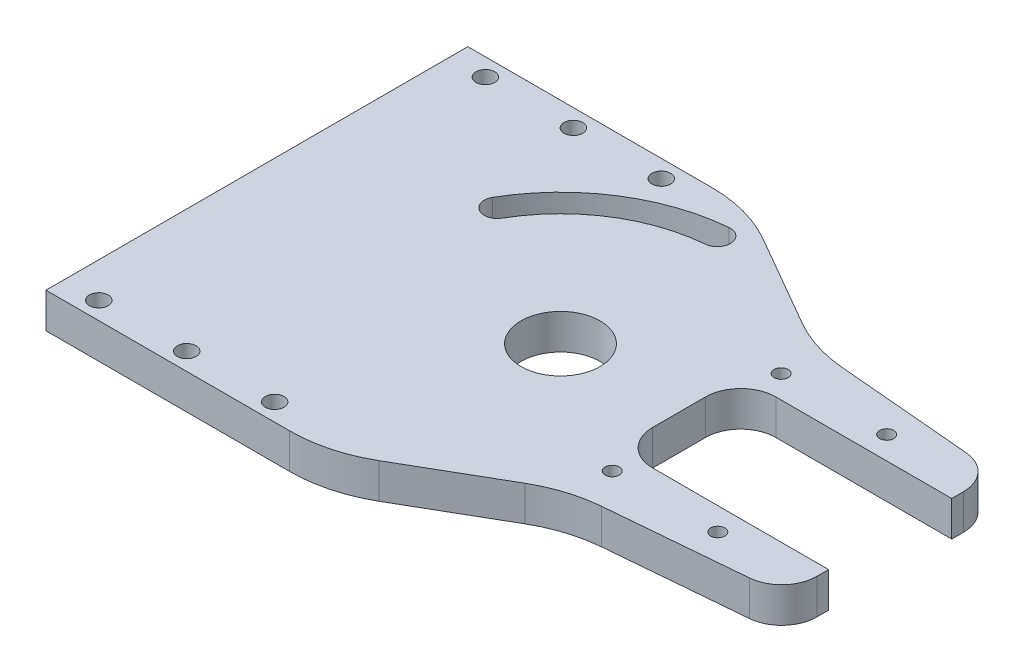
SolidWorks part; units mm, degrees
ref_plane "Front Plane" through (0, 0, 0) normal (0, 0, 1) x (1, 0, 0)
ref_plane "Top Plane" through (0, 0, 0) normal (0, 1, 0) x (1, 0, 0)
ref_plane "Right Plane" through (0, 0, 0) normal (1, 0, 0) x (0, 0, -1)
sketch "Sketch2" plane through (0, 0, 0) normal (0, 1, 0) x (1, 0, 0)
  line L0 (-114.3, 76.2) -> (-114.3, -76.2)
  line L1 (-114.3, 76.2) -> (114.3, 76.2)
  line L2 (114.3, 76.2) -> (114.3, -76.2)
  line L3 (-114.3, -76.2) -> (114.3, -76.2)
  line L6 (114.3, -76.2) -> (114.3, 76.2) construction
  line L7 (-114.3, -76.2) -> (114.3, 76.2) construction
  line L8 (-114.3, 76.2) -> (114.3, -76.2) construction
  point P5 (0, 0)
  dimension "D1" = 152.4
  dimension "D2" = 114.3
extrude "Boss-Extrude1" add sketch "Sketch2" against normal blind 12.7
sketch "Sketch4" plane through (0, 0, 0) normal (0, 1, 0) x (1, 0, 0)
  line L0 (114.3, 22.225) -> (114.3, -22.225)
  line L1 (114.3, -22.225) -> (38.1, -22.225)
  line L2 (114.3, 22.225) -> (38.1, 22.225)
  line L3 (38.1, 22.225) -> (38.1, -22.225)
  line L7 (114.3, 76.2) -> (114.3, 22.225)
  point P3 (38.1, 0)
  dimension "D1" = 76.2
  dimension "D2" = 44.45
extrude "Cut-Extrude1" cut sketch "Sketch4" against normal through all contours L2 L3 L1 L0
sketch "Sketch5" plane through (0, 0, 0) normal (0, 1, 0) x (1, 0, 0)
  circle A0 centre (-4.701, 0) radius 14.2875
  dimension "D1" = 28.575
extrude "Cut-Extrude2" cut sketch "Sketch5" against normal through all
sketch "Sketch8" plane through (0, 0, 0) normal (0, 1, 0) x (1, 0, 0)
  line L0 (114.3, -38.1) -> (-12.7, -49.2111)
  line L1 (-114.3, 76.2) -> (-114.3, -76.2) construction
  line L2 (114.3, -76.2) -> (114.3, -22.225) construction
  line L3 (-114.3, -76.2) -> (114.3, -76.2) construction
  line L4 (-114.3, -49.2111) -> (-114.3, -76.2)
  line L5 (114.3, -76.2) -> (114.3, -38.1)
  line L6 (-114.3, -76.2) -> (114.3, -76.2)
  line L7 (-114.3, -49.2111) -> (-12.7, -49.2111)
  dimension "D1" = 85
  dimension "D2" = 38.1
  dimension "D3" = 101.6
extrude "Cut-Extrude4" cut sketch "Sketch8" against normal through all
hole_wizard "Tap Drill for 1/4-20 Tap2" positions "Sketch10" profile "Sketch12" hole size "1/4-20" standard "ANSI Inch" end condition through all
sketch "Sketch10" plane through (0, 0, 0) normal (0, 1, 0) x (1, 0, 0)
  line L0 (114.3, -38.1) -> (114.3, -22.225) construction
  point P0 (82.55, -30.48)
  point P2 (44.45, -30.48)
  dimension "D1" = 7.62
  dimension "D2" = 38.1
  dimension "D3" = 31.75
sketch "Sketch12" plane through (82.55, 0, 30.48) normal (1, 0, 0) x (0, 0, 1)
  line L0 (0, 0) -> (0, 12.7)
  line L1 (0, 12.7) -> (2.5527, 12.7)
  line L2 (2.5527, 12.7) -> (2.5527, 0)
  line L5 (2.5527, 0) -> (0, 0)
  line L11 (0, -6.35) -> (0, 107.95) construction
  dimension "Thru Hole Dia." = 5.1054
  dimension "Thru Hole Depth" = 12.7
mirror "Mirror1" about plane through (0, 0, 0) normal (0, 0, 1) of "Tap Drill for 1/4-20 Tap2", "Cut-Extrude4"
fillet "Fillet1" radius 12.7 4 edges at (114.3, -6.35, -38.1) (114.3, -6.35, 38.1) (38.1, -6.35, 22.225) (38.1, -6.35, -22.225)
hole_wizard "Tap Drill for 1/4-20 Tap1" positions "Sketch13" profile "Sketch14" hole size "1/4-20" standard "ANSI Inch"
sketch "Sketch13" plane through (-114.3, 0, 0) normal (-1, 0, 0) x (0, 0, 1)
  line L0 (58.0999, -12.7) -> (58.0999, 0) construction
  line L2 (-44.45, -6.35) -> (44.45, -6.35)
  point P0 (-44.45, -6.35)
  point P2 (44.45, -6.35)
  point P8 (58.0999, -6.35)
  point P18 (0, -6.35)
  dimension "D1" = 88.9
sketch "Sketch14" plane through (-114.3, -6.35, -44.45) normal (0, 1, 0) x (0, 0, 1)
  line L0 (0, 0) -> (0, 14.2338)
  line L1 (0, 14.2338) -> (2.5527, 12.7)
  line L2 (2.5527, 12.7) -> (2.5527, 0)
  line L5 (2.5527, 0) -> (0, 0)
  line L10 (0, 14.2338) -> (-2.5527, 12.7) construction
  line L11 (0, -6.35) -> (0, 107.95) construction
  dimension "Hole Dia." = 5.1054
  dimension "Hole Depth" = 12.7
  dimension "Drill Angle" = 118
sketch "Sketch16" plane through (0, 0, 49.2111) normal (0, 0, 1) x (1, 0, 0)
  line L4 (-12.7, 0) -> (-114.3, 0)
  line L5 (-114.3, 0) -> (-114.3, -12.7)
  line L6 (-114.3, -12.7) -> (-12.7, -12.7)
  line L7 (-12.7, -12.7) -> (-12.7, 0)
  line L8 (-12.7, 0) -> (-114.3, 0)
  line L9 (-114.3, 0) -> (-114.3, -12.7)
  line L10 (-114.3, -12.7) -> (-12.7, -12.7)
  line L11 (-12.7, -12.7) -> (-12.7, 0)
  dimension "D1" = 0
extrude "Boss-Extrude2" add sketch "Sketch16" along normal blind 26.924
sketch "Sketch17" plane through (0, -12.7, 0) normal (0, -1, 0) x (1, 0, 0)
  line L0 (-12.7, 76.1351) -> (42.2625, 44.4025)
  line L1 (102.7069, 39.1143) -> (-12.7, 49.2111) construction
  line L2 (42.2625, 44.4025) -> (-12.7, 49.2111)
  line L3 (-12.7, 49.2111) -> (-12.7, 76.1351)
  line L4 (-114.3, 76.1351) -> (-12.7, 76.1351) construction
  dimension "D1" = 30
extrude "Boss-Extrude3" add sketch "Sketch17" against normal up to surface (12.7 mm away) up to face at (82.55, 0, -27.9273)
hole_wizard "1/4 Clearance Hole2" positions "Sketch18" profile "Sketch19" hole size "1/4" standard "ANSI Inch" end condition through all
sketch "Sketch18" plane through (0, 0, 0) normal (0, 1, 0) x (1, 0, 0)
  point P11 (-101.6, -69.7851)
  point P14 (-69.85, -69.7851)
  point P17 (-38.1, -69.7851)
sketch "Sketch19" plane through (-101.6, 0, 69.7851) normal (1, 0, 0) x (0, 0, 1)
  line L0 (0, 0) -> (0, 12.7)
  line L1 (0, 12.7) -> (3.3782, 12.7)
  line L2 (3.3782, 12.7) -> (3.3782, 0)
  line L5 (3.3782, 0) -> (0, 0)
  line L11 (0, -6.35) -> (0, 107.95) construction
  dimension "Thru Hole Dia." = 6.7564
  dimension "Thru Hole Depth" = 12.7
mirror "Mirror2" about plane through (0, 0, 0) normal (0, 0, 1) of "1/4 Clearance Hole2", "Boss-Extrude2", "Boss-Extrude3"
fillet "Fillet3" radius 50.8 4 edges at (-12.7, -6.35, 76.1351) (42.2625, -6.35, 44.4025) (-12.7, -6.35, -76.1351) (42.2625, -6.35, -44.4025)
sketch "Sketch20" plane through (0, 0, 0) normal (0, 1, 0) x (1, 0, 0)
  line L0 (-4.701, 0) -> (-58.5938, 31.115) construction
  line L1 (-10.1247, 61.9932) -> (-4.701, 0) construction
  line L2 (-4.701, 0) -> (85.299, 0) construction
  arc A0 (-10.1247, 61.9932) -> (-58.5938, 31.115) centre (-4.701, 0) ccw
  arc A1 (-10.5398, 66.7376) -> (-62.7182, 33.4963) centre (-4.701, 0) ccw
  arc A2 (-9.7096, 57.2488) -> (-54.4693, 28.7338) centre (-4.701, 0) ccw
  arc A3 (-10.5398, 66.7376) -> (-9.7096, 57.2488) centre (-10.1247, 61.9932) cw
  arc A4 (-62.7182, 33.4963) -> (-54.4693, 28.7338) centre (-58.5938, 31.115) ccw
  dimension "D2" = 62.23
  dimension "D4" = 4.7625
  dimension "D1" = 55
  dimension "D3" = 95
  dimension "D5" = 4.7625
extrude "Cut-Extrude5" cut sketch "Sketch20" against normal up to surface (12.7 mm away) contours A1 A4 A2 A3 up to face at (-4.701, -12.7, 14.2875)
